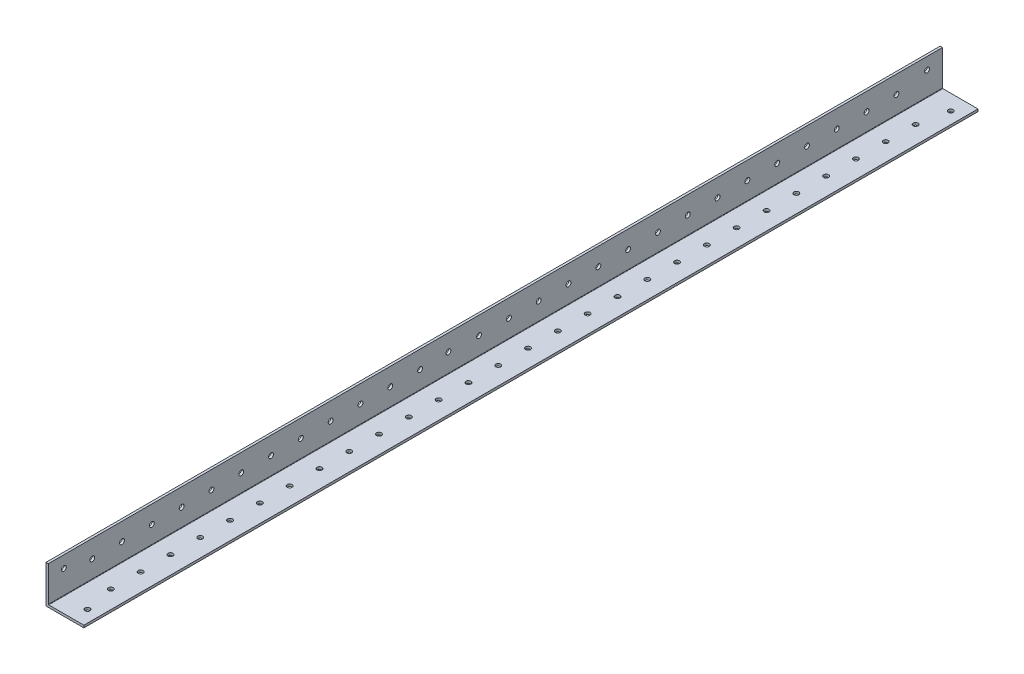
SolidWorks part; units mm, degrees
ref_plane "Front Plane" through (0, 0, 0) normal (0, 0, 1) x (1, 0, 0)
ref_plane "Top Plane" through (0, 0, 0) normal (0, 1, 0) x (1, 0, 0)
ref_plane "Right Plane" through (0, 0, 0) normal (1, 0, 0) x (0, 0, -1)
sketch "Sketch1" plane through (0, 0, 0) normal (0, 0, 1) x (1, 0, 0)
  line L0 (0, 25.4) -> (0, 0) construction
  line L1 (0, 0) -> (25.4, 0) construction
  line L2 (25.4, 0) -> (25.4, 1.5875) construction
  line L3 (25.4, 1.5875) -> (1.5875, 1.5875) construction
  line L4 (1.5875, 1.5875) -> (1.5875, 25.4) construction
  line L6 (1.5875, 25.4) -> (0, 25.4) construction
  arc A0 (1.5875, 1.8415) -> (1.8415, 1.5875) centre (1.8415, 1.8415) ccw construction
  point P4 (0, 0)
  dimension "Inside Corner Radius" = 0.254
  dimension "Outside Height" = 25.4
  dimension "Inside Height" = 23.8125
  dimension "Outside Width" = 25.4
  dimension "Inside Width" = 23.8125
  dimension "Wall Thickness" = 1.5875
  dimension "Shape" = 90
sketch "Sketch2" plane through (0, 0, 0) normal (1, 0, 0) x (0, 0, -1)
  line L0 (1219.2, 0) -> (-1219.2, 0) construction
  line L1 (-1219.2, 25.4) -> (-1219.2, 0) construction
  line L2 (1219.2, 25.4) -> (1219.2, 0) construction
  point P0 (-1189.99, 0)
  point P4 (0, 0)
  point P6 (1189.99, 0)
  dimension "D1" = 29.21
  dimension "D2" = 29.21
  dimension "D3" = 25.4
  dimension "Length" = 2438.4
sketch "Sketch3" plane through (0, 0, 0) normal (0, 0, 1) x (1, 0, 0)
  line L0 (1.5875, 25.4) -> (0, 25.4)
  line L1 (0, 25.4) -> (0, 0)
  line L2 (0, 0) -> (25.4, 0)
  line L3 (25.4, 0) -> (25.4, 1.5875)
  line L4 (25.4, 1.5875) -> (1.5875, 1.5875)
  line L5 (1.5875, 1.5875) -> (1.5875, 25.4)
extrude "Boss-Extrude1" add sketch "Sketch3" along normal mid plane 2438.4
fillet "Fillet1" radius 0.254 1 edges at (1.5875, 1.5875, 0)
sketch "Sketch4" plane through (0, 0, 0) normal (-1, 0, 0) x (0, 0, 1)
  line L0 (1219.2, 25.4) -> (1219.2, 0) construction
  line L1 (-1219.2, 0) -> (619.2, 0)
  line L2 (-1219.2, 0) -> (-1219.2, 74.9453)
  line L3 (-1219.2, 74.9453) -> (619.2, 74.9453)
  line L4 (619.2, 0) -> (619.2, 74.9453)
  dimension "D1" = 600
extrude "Cut-Extrude1" cut sketch "Sketch4" against normal blind 60
sketch "Sketch5" plane through (0, 1.5875, 0) normal (0, 1, 0) x (1, 0, 0)
  line L0 (17.4625, -1208.8241) -> (17.4625, -1189.2) construction
  line L1 (13.4937, -649.2) -> (13.4937, -629.5759) construction
  line L3 (1.5875, -1189.2) -> (25.4, -1189.2) construction
  line L4 (1.5875, -1219.2) -> (1.5875, -619.2) construction
  line L5 (25.4, -1219.2) -> (25.4, -619.2) construction
  line L6 (13.4937, -629.5759) -> (17.4625, -629.5759) construction
  line L7 (17.4625, -629.5759) -> (13.4937, -629.5759) construction
  circle A30 centre (17.4625, -629.5759) radius 1.65
  circle A31 centre (17.4625, -1208.8241) radius 1.65
  circle A32 centre (13.4938, -1189.2) radius 1.65
  circle A33 centre (13.4938, -1169.2) radius 1.65
  circle A34 centre (13.4938, -1149.2) radius 1.65
  circle A35 centre (13.4938, -1129.2) radius 1.65
  circle A36 centre (13.4938, -1109.2) radius 1.65
  circle A37 centre (13.4938, -1089.2) radius 1.65
  circle A38 centre (13.4938, -1069.2) radius 1.65
  circle A39 centre (13.4938, -1049.2) radius 1.65
  circle A40 centre (13.4938, -1029.2) radius 1.65
  circle A41 centre (13.4938, -1009.2) radius 1.65
  circle A42 centre (13.4938, -989.2) radius 1.65
  circle A43 centre (13.4938, -969.2) radius 1.65
  circle A44 centre (13.4938, -949.2) radius 1.65
  circle A45 centre (13.4938, -929.2) radius 1.65
  circle A46 centre (13.4938, -909.2) radius 1.65
  circle A47 centre (13.4938, -889.2) radius 1.65
  circle A48 centre (13.4938, -869.2) radius 1.65
  circle A49 centre (13.4938, -849.2) radius 1.65
  circle A50 centre (13.4938, -829.2) radius 1.65
  circle A51 centre (13.4938, -809.2) radius 1.65
  circle A52 centre (13.4938, -789.2) radius 1.65
  circle A53 centre (13.4938, -769.2) radius 1.65
  circle A54 centre (13.4938, -749.2) radius 1.65
  circle A55 centre (13.4938, -729.2) radius 1.65
  circle A56 centre (13.4938, -709.2) radius 1.65
  circle A57 centre (13.4938, -689.2) radius 1.65
  circle A58 centre (13.4938, -669.2) radius 1.65
  circle A59 centre (13.4937, -649.2) radius 1.65
  point P9 (0, 0)
  dimension "D1" = 3.3
  dimension "D2" = 3.3
  dimension "D3" = 28
  dimension "D4" = 20
extrude "Cut-Extrude2" cut sketch "Sketch5" against normal blind 10
sketch "Sketch9" plane through (1.5875, 0, 0) normal (1, 0, 0) x (0, 0, -1)
  line L0 (-1189.7652, 25.4) -> (-1189.7652, 1.5875) construction
  line L1 (-950.7063, 14.2875) -> (-950.7063, 1.5875) construction
  line L2 (-969.7652, 13.4937) -> (-950.7063, 13.4937) construction
  line L3 (-1207.4063, -6.3505) -> (-1204.0063, -6.3505) construction
  line L4 (-634.3937, -3.175) -> (-630.9937, -3.175) construction
  line L5 (-634.3937, 0) -> (-634.3937, -6.35) construction
  line L6 (-630.9937, -6.35) -> (-630.9937, 0) construction
  line L7 (-930.1411, 25.4) -> (-930.1411, 1.5875) construction
  line L8 (-1205.7063, -6.3505) -> (-1205.7063, 14.2875) construction
  line L9 (-1205.7063, 14.2875) -> (-950.7063, 14.2875) construction
  line L10 (-1219.2, 1.5875) -> (-619.2, 1.5875) construction
  line L11 (-950.7063, 5.2366) -> (-930.1411, 5.2366) construction
  line L12 (-1208.8241, 17.4625) -> (-1208.8241, 3.8186) construction
  line L13 (-1215.3265, 3.8186) -> (-1204.9125, 3.8186) construction
  line L14 (-1219.2, 25.4) -> (-619.2, 25.4) construction
  line L15 (-1208.8241, 8.3665) -> (-1189.7652, 8.3665) construction
  line L16 (-629.5759, 17.4625) -> (-629.5759, 3.8186) construction
  line L17 (-623.0735, 3.8186) -> (-633.4875, 3.8186) construction
  line L18 (-650.1411, 13.4937) -> (-629.5759, 13.4937) construction
  circle A0 centre (-629.5759, 17.4625) radius 1.65
  circle A3 centre (-1208.8241, 17.4625) radius 1.65
  circle A46 centre (-950.7063, 14.2875) radius 1.65
  circle A47 centre (-1189.7652, 13.4937) radius 1.65
  circle A48 centre (-1169.7652, 13.4937) radius 1.65
  circle A49 centre (-1149.7652, 13.4937) radius 1.65
  circle A50 centre (-1129.7652, 13.4937) radius 1.65
  circle A51 centre (-1109.7652, 13.4937) radius 1.65
  circle A52 centre (-1089.7652, 13.4937) radius 1.65
  circle A53 centre (-1069.7652, 13.4937) radius 1.65
  circle A54 centre (-1049.7652, 13.4937) radius 1.65
  circle A55 centre (-1029.7652, 13.4937) radius 1.65
  circle A56 centre (-1009.7652, 13.4937) radius 1.65
  circle A57 centre (-989.7652, 13.4937) radius 1.65
  circle A58 centre (-969.7652, 13.4937) radius 1.65
  circle A59 centre (-930.1411, 13.4937) radius 1.65
  circle A60 centre (-910.1411, 13.4937) radius 1.65
  circle A61 centre (-890.1411, 13.4937) radius 1.65
  circle A62 centre (-870.1411, 13.4937) radius 1.65
  circle A63 centre (-850.1411, 13.4937) radius 1.65
  circle A64 centre (-830.1411, 13.4937) radius 1.65
  circle A65 centre (-810.1411, 13.4937) radius 1.65
  circle A66 centre (-790.1411, 13.4937) radius 1.65
  circle A67 centre (-770.1411, 13.4937) radius 1.65
  circle A68 centre (-750.1411, 13.4937) radius 1.65
  circle A69 centre (-730.1411, 13.4937) radius 1.65
  circle A70 centre (-710.1411, 13.4937) radius 1.65
  circle A71 centre (-690.1411, 13.4937) radius 1.65
  circle A72 centre (-670.1411, 13.4937) radius 1.65
  circle A73 centre (-650.1411, 13.4937) radius 1.65
  dimension "D1" = 12.7
  dimension "D3" = 3.3
  dimension "D4" = 3.3
  dimension "D7" = 3.3
  dimension "D2" = 255
  dimension "D5" = 20
  dimension "D6" = 12
  dimension "D8" = 20
extrude "Cut-Extrude6" cut sketch "Sketch9" against normal blind 60
equation "\"D1@Boss-Extrude1\"=\"Length@Sketch2\""
equation "\"D1@Sketch2\" = \"Outside Width@Sketch1\" * 1.15"
equation "\"D2@Sketch2\"=\"D1@Sketch2\""
equation "\"D1@Fillet1\"=\"Inside Corner Radius@Sketch1\""
equation "\"D3@Sketch2\"=\"Outside Height@Sketch1\""
